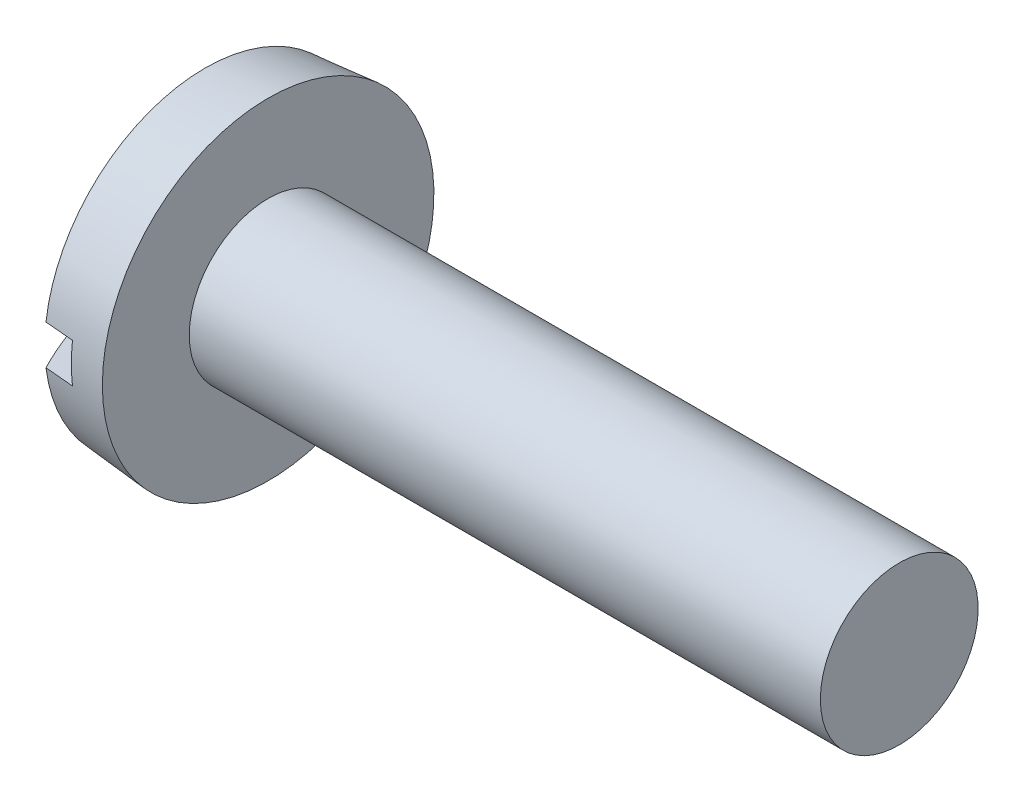
SolidWorks part; units mm, degrees
ref_plane "Plane1" through (0, 0, 0) normal (0, 0, 1) x (1, 0, 0)
ref_plane "Plane2" through (0, 0, 0) normal (0, 1, 0) x (1, 0, 0)
ref_plane "Plane3" through (0, 0, 0) normal (1, 0, 0) x (0, 0, -1)
sketch "BodySke" plane through (0, 0, 0) normal (0, 0, 1) x (1, 0, 0)
  line L0 (6.1976, 4.7625) -> (6.1976, 10.0076)
  line L1 (6.1976, 10.0076) -> (2.3876, 9.6743)
  line L2 (-25.4, 0) -> (127, 0) construction
  line L3 (6.1976, -10.0076) -> (2.3876, -9.6743) construction
  line L4 (6.1976, 4.7625) -> (44.2976, 4.7625)
  line L5 (44.2976, 4.7625) -> (44.2976, 0)
  line L6 (44.2976, 0) -> (0, 0)
  line L7 (6.1976, -4.7625) -> (44.2976, -4.7625) construction
  line L8 (7.7851, 6.35) -> (7.7851, -3.175) construction
  line L9 (18.8976, 6.35) -> (18.8976, -3.175) construction
  arc A0 (0, 0) -> (2.3876, 9.6743) centre (20.7933, 0) cw
  dimension "Diameter" = 9.525
  dimension "Advance" = 1.5875
revolve "Base-Revolve" add sketch "BodySke" angle 360 about L2
cosmetic thread "ThreadCosmetic" [suppressed] parameters "Thread_length"=25.4, "Thread_minor"=7.9375
sketch "Sketch2" plane through (0, 0, 0) normal (1, 0, 0) x (0, 0, -1)
  line L0 (10.0076, -1.1938) -> (10.0076, 1.1938)
  line L1 (10.0076, 1.1938) -> (-10.0076, 1.1938)
  line L2 (-10.0076, 1.1938) -> (-10.0076, -1.1938)
  line L3 (-10.0076, -1.1938) -> (10.0076, -1.1938)
  dimension "D1" = 20.0152
  dimension "D2" = 10.0076
  dimension "D3" = 1.1938
extrude "Slot" cut sketch "Sketch2" along normal blind 4.1402
sketch "Sketch3" plane through (0, 0, 0) normal (1, 0, 0) x (0, 0, -1)
  line L0 (-1.0287, 6.096) -> (1.0287, 6.096)
  line L1 (1.0287, 6.096) -> (1.0287, -6.096)
  line L2 (1.0287, -6.096) -> (-1.0287, -6.096)
  line L3 (-1.0287, -6.096) -> (-1.0287, 6.096)
  dimension "D1" = 1.0287
  dimension "D2" = 6.096
ref_plane "Plane4" through (7.2644, 0, 0) normal (1, 0, 0) x (0, 0, -1)
sketch "Sketch4" plane through (7.2644, 0, 0) normal (1, 0, 0) x (0, 0, -1)
  line L0 (-0.5143, 0.5143) -> (0.5143, 0.5143)
  line L1 (0.5143, 0.5143) -> (0.5144, -0.5143)
  line L2 (0.5144, -0.5143) -> (-0.5143, -0.5144)
  line L3 (-0.5143, -0.5144) -> (-0.5143, 0.5143)
  dimension "D1" = 1.0287
  dimension "D2" = 0.5143
  dimension "D3" = 1.0287
  dimension "D4" = 0.5143
loft "Cross" cut profiles "Sketch3", "Sketch4"
pattern_circular "CirPattern1" count 2 every 90 about axis through (-25.4, 0, 0) along (1, 0, 0) of "Cross"
sketch "ThdSchSke" plane through (0, 0, 0) normal (0, 0, 1) x (1, 0, 0)
  line L0 (18.8976, -3.9688) -> (18.3418, -4.7625)
  line L1 (18.8976, -3.9688) -> (19.4534, -4.7625)
  line L2 (19.4534, -4.7625) -> (19.4534, -5.9531)
  line L3 (-3.175, 0) -> (5.1513, 0) construction
  line L5 (19.4534, -5.9531) -> (18.3418, -5.9531)
  line L6 (18.3418, -5.9531) -> (18.3418, -4.7625)
  dimension "Thread_minor" = 7.9375
  dimension "Diameter" = 9.525
  dimension "Start" = 18.8976
revolve "ThreadSchematic" [suppressed] cut sketch "ThdSchSke" angle 360 about L3
pattern_linear "ThdSchPat" [suppressed]
equation "\"D1@Sketch3\" = \"Cross_width@Sketch3\" / 2"
equation "\"D2@Sketch3\" = \"Cross_dia@Sketch3\" / 2"
equation "\"D1@Sketch4\" = \"Cross_width@Sketch3\"*.5"
equation "\"D2@Sketch4\" = \"D1@Sketch4\" / 2"
equation "\"D3@Sketch4\" = \"D1@Sketch4\""
equation "\"D4@Sketch4\" = \"D2@Sketch4\""
equation "\"D1@Sketch2\" = \"Head_dia@BodySke\""
equation "\"D2@Sketch2\" = \"D1@Sketch2\" / 2"
equation "\"D3@Sketch2\" = \"Slot_width@Sketch2\" / 2"
equation "\"Thread_length@ThreadCosmetic\" = ((sgn( (\"Length@BodySke\" - \"Advance@BodySke\" ) - \"Thread_nom@BodySke\" )-1)*( (\"Length@BodySke\" - \"Advance@BodySke\" ) - \"Thread_nom@BodySke\" ))/-2+ \"Thread_nom@BodySke\""
equation "\"Thread_minor@ThdSchSke\" = \"Thread_minor@ThreadCosmetic\""
equation "\"Diameter@ThdSchSke\" = \"Diameter@BodySke\""
equation "\"Overcut@ThdSchSke\" = \"Diameter@BodySke\" * 1.25"
equation "\"Start@ThdSchSke\" = \"Head_ht@BodySke\" + \"Length@BodySke\" - \"Thread_length@ThreadCosmetic\"  '---Non-countersunk---"
equation "\"Num_threads@ThdSchPat\" = int( \"Thread_length@ThreadCosmetic\" / \"Advance@BodySke\" + 0.999 )  + 1"
equation "\"Advance@ThdSchPat\" = \"Thread_length@ThreadCosmetic\" /  (\"Num_threads@ThdSchPat\" - 1) 'relax it"
